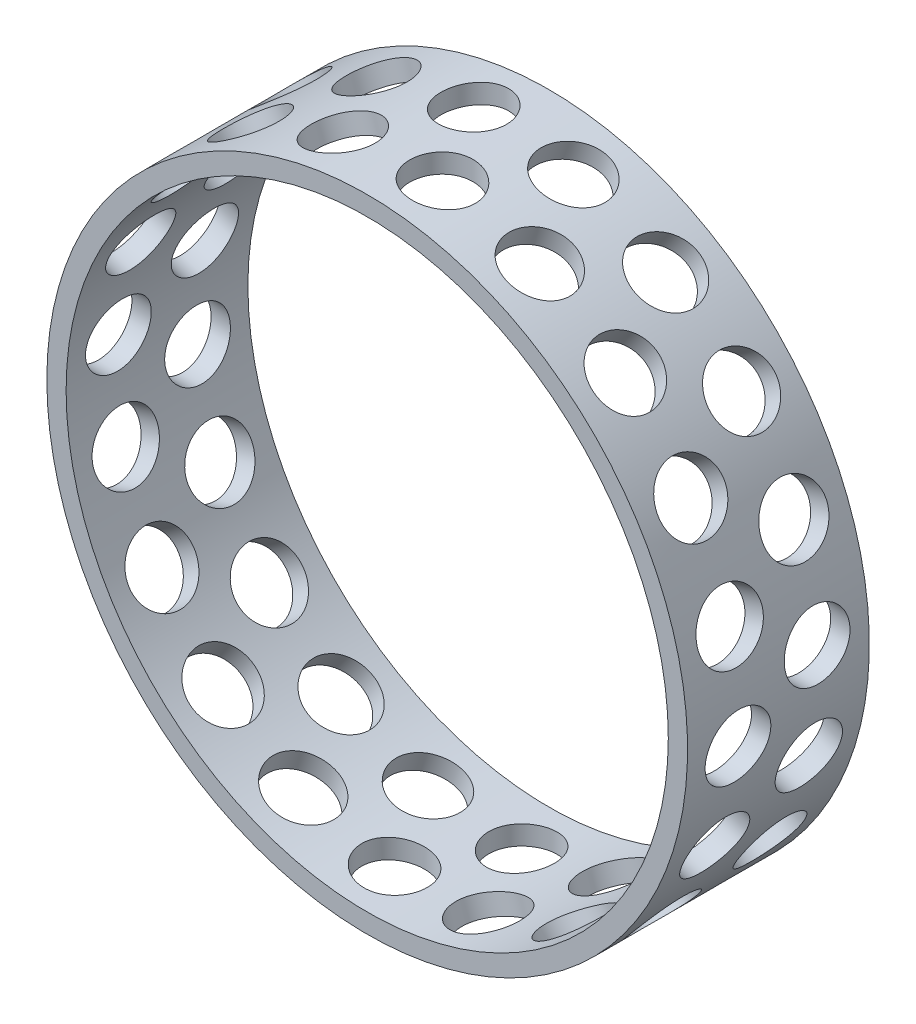
SolidWorks part; units mm, degrees
material "Plain Carbon Steel"
ref_plane "Front Plane" through (0, 0, 0) normal (0, 0, 1) x (1, 0, 0)
ref_plane "Top Plane" through (0, 0, 0) normal (0, 1, 0) x (1, 0, 0)
ref_plane "Right Plane" through (0, 0, 0) normal (1, 0, 0) x (0, 0, -1)
sketch "Sketch1" plane through (0, 0, 0) normal (1, 0, 0) x (0, 0, -1)
  line L0 (1, 83.0999) -> (48.15, 83.0999)
  line L1 (48.15, 83.0999) -> (48.15, 78.0999)
  line L2 (48.15, 78.0999) -> (1, 78.0999)
  line L3 (1, 78.0999) -> (1, 83.0999)
  dimension "D1" = 83.0999
  dimension "D2" = 5
  dimension "D3" = 47.15
  dimension "D4" = 1
ref_axis "Axis1" through (0, 0, -50.5075) along (0, 0, 1)
revolve "Revolve1" add sketch "Sketch1" angle 360 about axis through (0, 0, -50.5075) along (0, 0, 1)
sketch "Sketch2" plane through (0, 0, 0) normal (1, 0, 0) x (0, 0, -1)
  line L0 (14.3098, 6.2149) -> (24.575, 0) construction
  line L1 (50.5075, 0) -> (-1.3575, 0) construction
  line L2 (24.575, 0) -> (34.8402, -6.2149) construction
  line L3 (1, 83.0999) -> (1, -83.0999) construction
  circle A0 centre (14.3098, 6.2149) radius 8.5
  circle A1 centre (34.8402, -6.2149) radius 8.5
  dimension "D1" = 17
  dimension "D2" = 12
  dimension "D3" = 23.575
extrude "Cut-Extrude1" cut sketch "Sketch2" against normal through all
pattern_circular "CirPattern1" count 20 over 360 about axis through (0, 0, -50.5075) along (0, 0, 1) of "Cut-Extrude1"
equation "\"TubeDiameter\" = 6.5433in"
equation "\"D1@Sketch1\"=\"TubeDiameter\"/2"
